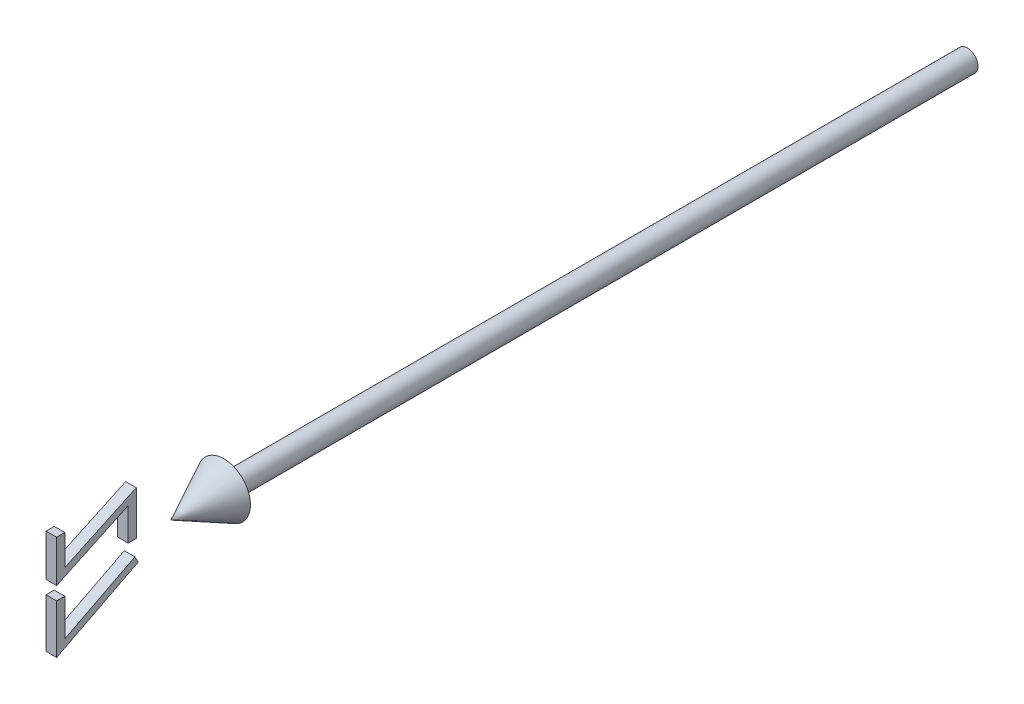
SolidWorks part; units mm, degrees
ref_plane "Front Plane" through (0, 0, 0) normal (0, 0, 1) x (1, 0, 0)
ref_plane "Top Plane" through (0, 0, 0) normal (0, 1, 0) x (1, 0, 0)
ref_plane "Right Plane" through (0, 0, 0) normal (1, 0, 0) x (0, 0, -1)
sketch "Sketch2" plane through (0, 0, 0) normal (0, 1, 0) x (1, 0, 0)
  line L0 (0, 41.95) -> (0, -114.4521) construction
  line L1 (-36.8894, 0) -> (41.4965, 0) construction
  line L2 (0, -150) -> (5, -140)
  line L3 (5, -140) -> (2, -140)
  line L4 (2, -140) -> (2, 0)
  line L5 (2, 0) -> (0, 0)
  line L6 (0, 0) -> (0, -150)
  dimension "D1" = 150
  dimension "D2" = 2
  dimension "D3" = 10
  dimension "D4" = 5
revolve "Revolve1" add sketch "Sketch2" angle 360 about L0
sketch "Sketch3" plane through (0, 0, 0) normal (1, 0, 0) x (0, -1, 0)
  line L0 (0, -101.5706) -> (0, -127.8138) construction
  line L1 (-10.1124, -157.5) -> (14.1256, -157.5) construction
  line L2 (-22.6169, 0) -> (17.7708, 0) construction
  text T0 "Z7\r\n" font "Century Gothic" height 15
  dimension "D1" = 157.5
extrude "Boss-Extrude1" add sketch "Sketch3" against normal blind 1 and the other way blind 1 separate body
equation "\"D1@Sketch2\"=\"frame_arrow_length\""
equation "\"D2@Sketch2\"=\"frame_arrow_odA\"/2"
equation "\"D4@Sketch2\"=\"frame_arrow_head_od\""
equation "\"D3@Sketch2\"=\"frame_arrow_head_length\""
equation "\"frame_arrow_length\"=150"
equation "\"frame_arrow_head_length\"=10"
equation "\"frame_arrow_head_od\"=5"
equation "\"frame_arrow_odA\"=4"
equation "\"D1@Sketch3\"=\"frame_arrow_length\"*1.05"
